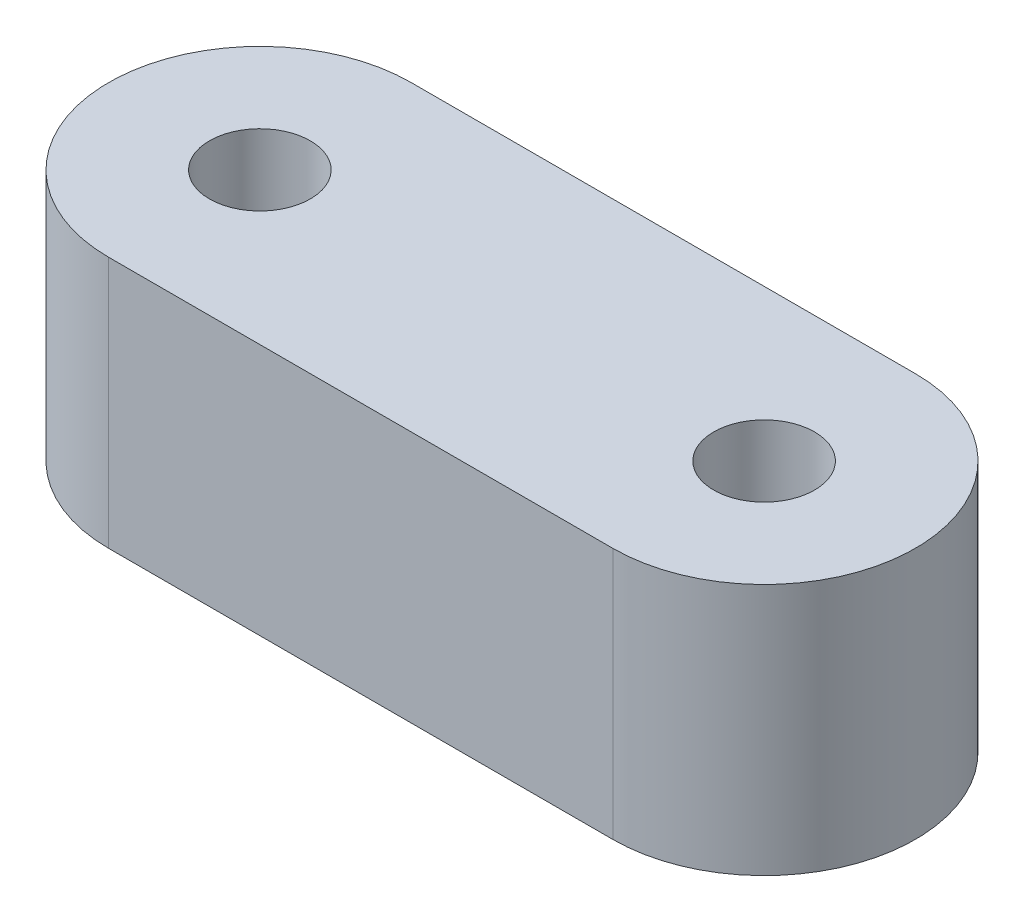
SolidWorks part; units mm, degrees
ref_plane "Front Plane" through (0, 0, 0) normal (0, 0, 1) x (1, 0, 0)
ref_plane "Top Plane" through (0, 0, 0) normal (0, 1, 0) x (1, 0, 0)
ref_plane "Right Plane" through (0, 0, 0) normal (1, 0, 0) x (0, 0, -1)
sketch "Sketch3" plane through (0, 0, 0) normal (0, 1, 0) x (1, 0, 0)
  line L0 (-63.5, 0) -> (-38.1, 0) construction
  line L1 (-6.985, 0) -> (6.985, 0) construction
  line L2 (-63.5, 7.62) -> (-38.1, 7.62)
  line L3 (-63.5, -7.62) -> (-38.1, -7.62)
  arc A0 (-63.5, 7.62) -> (-63.5, -7.62) centre (-63.5, 0) ccw
  arc A1 (-38.1, -7.62) -> (-38.1, 7.62) centre (-38.1, 0) ccw
  point P5 (-50.8, 0)
  point P10 (0, 0)
  point P11 (0, 0)
  dimension "D2" = 7.62
  dimension "D3" = 63.5
extrude "Boss-Extrude1" add sketch "Sketch3" along normal blind 12.7
sketch "Sketch4" plane through (0, 12.7, 0) normal (0, 1, 0) x (1, 0, 0)
  circle A0 centre (-63.5, 0) radius 2.54
  circle A1 centre (-38.1, 0) radius 2.54
  point P3 (0, 0)
  point P7 (0, 0)
  dimension "D1" = 5.08
extrude "Cut-Extrude3" cut sketch "Sketch4" against normal through all
equation "\"TibiaLength\"= 5in"
equation "\"TibiaRadius\"= 0.3in"
equation "\"TibiaDistFromCentre\"= \"TibiaLength\" / 2"
equation "\"TibiaThickness\"= 0.5in"
equation "\"HoleRadius\"= 0.2in"
equation "\"D1@Sketch3\"= \"TibiaLength\" * 0.2"
equation "\"D2@Sketch3\"= \"TibiaRadius\""
equation "\"D3@Sketch3\"= \"TibiaDistFromCentre\""
equation "\"D1@Boss-Extrude1\"= \"TibiaThickness\""
equation "\"D1@Sketch4\"= \"HoleRadius\""
